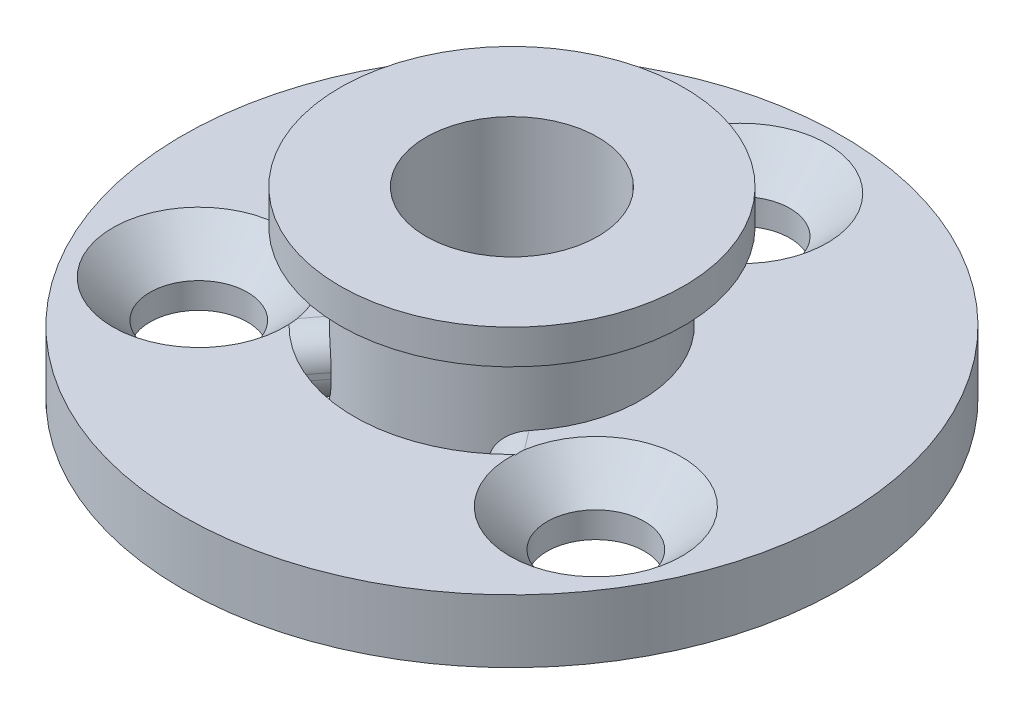
SolidWorks part; units mm, degrees
ref_plane "Plan de face" through (0, 0, 0) normal (0, 0, 1) x (1, 0, 0)
ref_plane "Plan de dessus" through (0, 0, 0) normal (0, 1, 0) x (1, 0, 0)
ref_plane "Plan de droite" through (0, 0, 0) normal (1, 0, 0) x (0, 0, -1)
sketch "Esquisse1" plane through (0, 0, 0) normal (0, 0, 1) x (1, 0, 0)
  line L0 (0, 4.6899) -> (0, -3.9873) construction
  line L1 (3, -3.2) -> (3, 3.2)
  line L2 (3, 3.2) -> (6, 3.2)
  line L3 (6, 3.2) -> (6, 2)
  line L4 (6, 2) -> (4.5, 2)
  line L5 (4.5, 2) -> (4.5, -1)
  line L6 (4.5, -1) -> (11.5, -1)
  line L7 (11.5, -1) -> (11.5, -3.2)
  line L8 (11.5, -3.2) -> (3, -3.2)
  point P5 (4.5, 0.5)
  point P12 (3, 0)
  dimension "D1" = 1.2
  dimension "D2" = 2.2
  dimension "D3" = 3
  dimension "D4" = 3
  dimension "D5" = 1.5
  dimension "D6" = 1.5
  dimension "D7" = 11.5
revolve "Révolution1" add sketch "Esquisse1" angle 360 about L0
sketch "Esquisse2" plane through (0, -1, 0) normal (0, 1, 0) x (1, 0, 0)
  line L0 (0, 0) -> (0, 8) construction
  line L1 (0, 0) -> (6.9282, -4) construction
  line L2 (0, 0) -> (-6.9282, -4) construction
  circle A0 centre (0, 0) radius 8 construction
  circle A1 centre (0, 8) radius 1.7 construction
  circle A2 centre (0, 8) radius 2.85 construction
  circle A3 centre (6.9282, -4) radius 2.85 construction
  circle A4 centre (6.9282, -4) radius 1.7 construction
  circle A5 centre (-6.9282, -4) radius 2.85 construction
  circle A6 centre (-6.9282, -4) radius 1.7 construction
  point P14 (0, 0)
  dimension "D1" = 16
  dimension "D2" = 3.4
  dimension "D3" = 5.7
  dimension "D4" = 3
hole_wizard "CSK for M3 Flat Head Machine Screw1" positions "Esquisse5" profile "Esquisse4" countersink size "M3" standard "ANSI Metric" end condition through all
sketch "Esquisse5" plane through (0, -1, 0) normal (0, 1, 0) x (1, 0, 0)
  point P0 (-6.9282, -4)
  point P3 (6.9282, -4)
  point P6 (0, 8)
sketch "Esquisse4" plane through (-6.9282, -1, 4) normal (1, 0, 0) x (0, 0, 1)
  line L0 (0, 0) -> (0, 2.2)
  line L1 (0, 2.2) -> (1.7, 2.2)
  line L2 (1.7, 2.2) -> (1.7, 1.3)
  line L3 (1.7, 1.3) -> (3, 0)
  line L5 (3, 0) -> (0, 0)
  line L6 (-1.7, 1.3) -> (-3, 0) construction
  line L11 (0, -6.35) -> (0, 107.95) construction
  dimension "Thru Hole Dia." = 3.4
  dimension "Thru Hole Depth" = 2.2
  dimension "Near C'Sink Dia." = 6
  dimension "Near C'Sink Angle" = 90
sketch "Esquisse6" plane through (0, -1, 0) normal (0, 1, 0) x (1, 0, 0)
  line L0 (2.7394, -3.5701) -> (3.3482, -4.3634)
  line L1 (-2.7394, -3.5701) -> (-3.3482, -4.3634)
  line L2 (0, 0) -> (0, -11.5) construction
  arc A0 (2.7394, -3.5701) -> (-2.7394, -3.5701) centre (0, 0) cw
  arc A1 (-3.3482, -4.3634) -> (3.3482, -4.3634) centre (0, 0) ccw
  circle A2 centre (0, 0) radius 4.5 construction
  circle A3 centre (0, 0) radius 11.5 construction
  dimension "D1" = 1
  dimension "D2" = 37.5
  dimension "D3" = 37.5
extrude "Enlèv. mat.-Extru.1" cut sketch "Esquisse6" against normal through all
fillet "Congé1" radius 1 4 edges at (3.0438, -3.2, 3.9668) (-3.0438, -3.2, 3.9668) (-3.0438, -1, 3.9668) (3.0438, -1, 3.9668)
